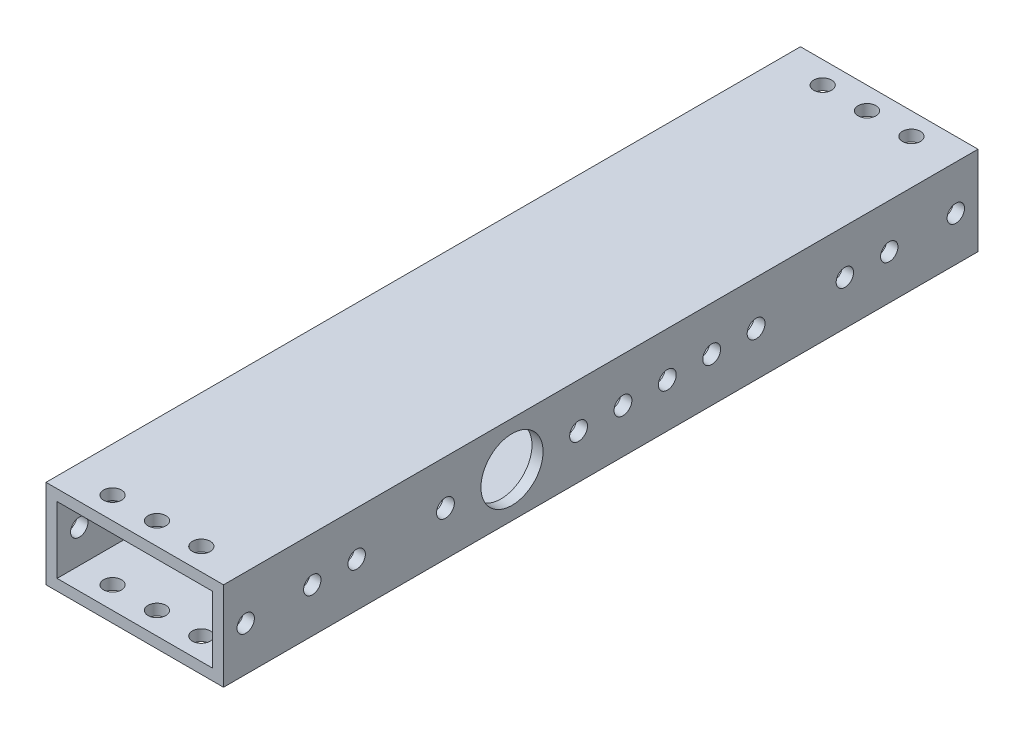
SolidWorks part; units mm, degrees
material "6061-T6 (SS)"
ref_plane "Front Plane" through (0, 0, 0) normal (0, 0, 1) x (1, 0, 0)
ref_plane "Top Plane" through (0, 0, 0) normal (0, 1, 0) x (1, 0, 0)
ref_plane "Right Plane" through (0, 0, 0) normal (1, 0, 0) x (0, 0, -1)
sketch "Sketch1" plane through (0, 0, 0) normal (0, 0, 1) x (1, 0, 0)
  line L0 (-22.225, 9.525) -> (22.225, 9.525)
  line L1 (-25.4, -12.7) -> (25.4, -12.7)
  line L2 (-25.4, -12.7) -> (-25.4, 12.7)
  line L3 (-25.4, 12.7) -> (25.4, 12.7)
  line L4 (25.4, -12.7) -> (25.4, 12.7)
  line L5 (-25.4, -12.7) -> (25.4, 12.7) construction
  line L6 (-25.4, 12.7) -> (25.4, -12.7) construction
  line L7 (22.225, -9.525) -> (22.225, 9.525)
  line L8 (-22.225, -9.525) -> (22.225, -9.525)
  line L9 (-22.225, -9.525) -> (-22.225, 9.525)
  point P0 (0, 0)
  dimension "D1" = 50.8
  dimension "D2" = 25.4
  dimension "D3" = 3.175
extrude "Boss-Extrude1" add sketch "Sketch1" along normal mid plane 215.9
sketch "Sketch3" plane through (0, 12.7, 0) normal (0, 1, 0) x (1, 0, 0)
  line L0 (-25.4, 0) -> (25.4, 0) construction
  line L1 (-25.4, -107.95) -> (-25.4, 107.95) construction
  line L2 (25.4, -107.95) -> (25.4, 107.95) construction
  line L3 (25.4, -107.95) -> (-25.4, -107.95) construction
  circle A0 centre (-12.7, -101.6) radius 2.5527
  circle A1 centre (0, -101.6) radius 2.5527
  circle A2 centre (12.7, -101.6) radius 2.5527
  circle A3 centre (12.7, 101.6) radius 2.5527
  circle A4 centre (0, 101.6) radius 2.5527
  circle A5 centre (-12.7, 101.6) radius 2.5527
  dimension "D1" = 5.1054
  dimension "D2" = 12.7
  dimension "D3" = 12.7
  dimension "D4" = 6.35
extrude "Cut-Extrude2" cut sketch "Sketch3" against normal through all
sketch "Sketch4" plane through (25.4, 0, 0) normal (1, 0, 0) x (0, 0, -1)
  line L0 (-25.4, 0) -> (-45.1908, 0) construction
  line L1 (-16.51, 0) -> (-34.29, 0) construction
  line L8 (-25.4, 0) -> (31.75, 0) construction
  line L9 (0, 12.7) -> (0, -12.7) construction
  line L10 (-107.95, 12.7) -> (107.95, 12.7) construction
  line L11 (-107.95, -12.7) -> (107.95, -12.7) construction
  circle A0 centre (-25.4, 0) radius 8.89
  circle A9 centre (31.75, 0) radius 2.5527
  circle A10 centre (19.05, 0) radius 2.5527
  dimension "D2" = 17.78
  dimension "D3" = 25.4
  dimension "D1" = 57.15
  dimension "D4" = 5.1054
  dimension "D6" = 44.45
extrude "Cut-Extrude3" cut sketch "Sketch4" against normal through all contours A0 | A9 | A10
sketch "Sketch2" plane through (25.4, 0, 0) normal (1, 0, 0) x (0, 0, -1)
  line L0 (-107.95, -12.7) -> (-107.95, 12.7) construction
  line L1 (0, 12.7) -> (0, -12.7) construction
  line L2 (-107.95, 12.7) -> (107.95, 12.7) construction
  line L3 (-107.95, -12.7) -> (107.95, -12.7) construction
  circle A0 centre (-101.6, 0) radius 2.4892
  circle A1 centre (101.6, 0) radius 2.4892
  circle A2 centre (-82.55, 0) radius 2.4892
  circle A3 centre (-69.85, 0) radius 2.4892
  circle A4 centre (69.85, 0) radius 2.4892
  circle A5 centre (82.55, 0) radius 2.4892
  dimension "D2" = 4.9784
  dimension "D5" = 4.9784
  dimension "D4" = 25.4
  dimension "D1" = 6.35
  dimension "D3" = 12.7
extrude "Cut-Extrude1" cut sketch "Sketch2" against normal through all
sketch "Sketch5" plane through (0, -12.7, 0) normal (0, -1, 0) x (1, 0, 0)
  line L0 (-25.4, 107.95) -> (-25.4, -107.95) construction
  line L1 (-25.4, 107.95) -> (25.4, 107.95) construction
  line L4 (25.4, 25.4) -> (-25.4, 25.4) construction
  line L5 (25.4, 107.95) -> (25.4, -107.95) construction
  circle A0 centre (-3.81, 69.85) radius 2.4892
  circle A1 centre (-16.51, 69.85) radius 2.4892
  circle A2 centre (-16.51, 57.15) radius 2.4892
  circle A3 centre (-3.81, 57.15) radius 2.4892
  circle A8 centre (-3.81, -6.35) radius 2.4892
  circle A9 centre (-16.51, -6.35) radius 2.4892
  circle A10 centre (-16.51, -19.05) radius 2.4892
  circle A11 centre (-3.81, -19.05) radius 2.4892
  dimension "D3" = 4.9784
  dimension "D4" = 8.89
  dimension "D7" = 12.7
  dimension "D12" = 82.55
  dimension "D5" = 31.75
  dimension "D6" = 12.7
  dimension "D1" = 2
  dimension "D2" = 2
extrude "Cut-Extrude4" cut sketch "Sketch5" against normal up to next
sketch "Sketch7" plane through (25.4, 0, 0) normal (1, 0, 0) x (0, 0, -1)
  circle A0 centre (44.45, 0) radius 2.5527
  circle A1 centre (31.75, 0) radius 2.5527 construction
  circle A5 centre (6.35, 0) radius 2.5527
  circle A6 centre (-6.35, 0) radius 2.5527
  circle A7 centre (-44.45, 0) radius 2.5527
  circle A8 centre (-25.4, 0) radius 8.89 construction
  dimension "D1" = 12.7
  dimension "D2" = 19.05
  dimension "D3" = 19.05
  dimension "D4" = 12.7
extrude "Cut-Extrude5" cut sketch "Sketch7" against normal up to next contours A0 | A7 | A6 | A5
